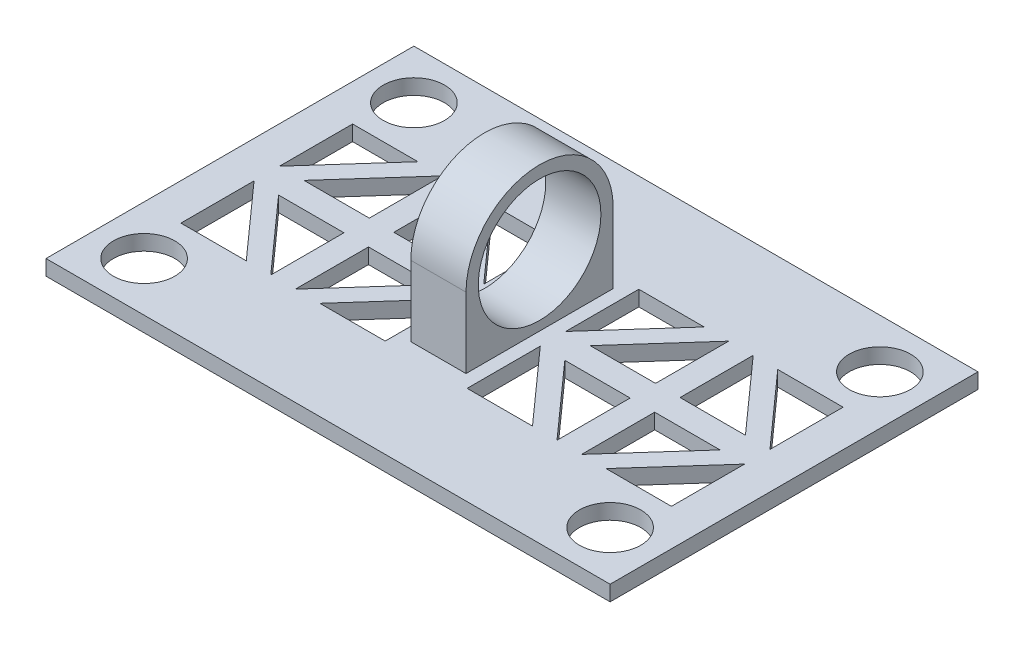
SolidWorks part; units mm, degrees
note: '?' marks a value the reader was unsure of.
ref_plane "Front Plane" through (0, 0, 0) normal (0, 0, 1) x (1, 0, 0)
ref_plane "Top Plane" through (0, 0, 0) normal (0, 1, 0) x (1, 0, 0)
ref_plane "Right Plane" through (0, 0, 0) normal (1, 0, 0) x (0, 0, -1)
sketch "Sketch1" plane through (0, 0, 0) normal (0, 1, 0) x (1, 0, 0)
  line L1 (0, 0) -> (-58.42, 0)
  line L2 (0, 0) -> (0, 38.1)
  line L3 (0, 38.1) -> (-58.42, 38.1)
  line L4 (-58.42, 0) -> (-58.42, 38.1)
  dimension "D1" = 58.42
  dimension "D2" = 38.1
extrude "Boss-Extrude1" add sketch "Sketch1" along normal blind 1.5875 contours L3 L4 L1 L2
ref_plane "Plane1" through (-29.21, 0, 0) normal (1, 0, 0) x (0, 0, -1)
sketch "Sketch2" plane through (-29.21, 0, 0) normal (1, 0, 0) x (0, 0, -1)
  line L0 (0, 0) -> (38.1, 0) construction
  line L1 (11.43, 8.89) -> (11.43, 0)
  line L2 (26.67, 8.89) -> (26.67, 0)
  line L3 (0, 0) -> (38.1, 0) construction
  line L4 (11.43, 0) -> (26.67, 0) construction
  line L5 (11.43, 0) -> (26.67, 0)
  circle A0 centre (19.05, 8.89) radius 7.62 construction
  arc A1 (11.43, 8.89) -> (26.67, 8.89) centre (19.05, 8.89) cw
  circle A2 centre (19.05, 8.89) radius 6.35
  point P13 (19.05, 0)
  point P15 (19.05, 0)
  dimension "D2" = 15.24
  dimension "D3" = 8.89
  dimension "D4" = 12.7
  dimension "D1" = 38.1
extrude "Boss-Extrude2" add sketch "Sketch2" along normal mid plane 5.715 contours A1 L2 L5 L1
sketch "Sketch4" plane through (-26.3525, 0, 0) normal (1, 0, 0) x (0, 0, -1)
  line L0 (19.05, 16.51) -> (19.05, 1.5875) construction
  line L1 (26.67, 1.5875) -> (11.43, 1.5875) construction
  line L2 (11.43, 8.89) -> (26.67, 8.89) construction
  arc A0 (26.67, 8.89) -> (11.43, 8.89) centre (19.05, 8.89) ccw construction
  circle A1 centre (19.05, 8.89) radius 6.35
  point P11 (19.05, 8.89)
  point P14 (0, 0)
  point P15 (0, 0)
  point P16 (19.05, 8.89)
  point P17 (19.05, 8.89)
  dimension "D1" = 12.7
extrude "Cut-Extrude1" cut sketch "Sketch4" against normal through all
sketch "Sketch5" plane through (0, 1.5875, 0) normal (0, 1, 0) x (1, 0, 0)
  line L0 (-54.61, 27.94) -> (-54.61, 20.3635)
  line L1 (-54.61, 20.3635) -> (-47.8408, 27.94)
  line L2 (-47.8408, 27.94) -> (-54.61, 27.94)
  line L3 (-45.3008, 27.94) -> (-52.07, 20.3635)
  line L4 (-52.07, 20.3635) -> (-45.3008, 20.3635)
  line L5 (-45.3008, 20.3635) -> (-45.3008, 27.94)
  line L6 (-42.7608, 20.3635) -> (-42.7608, 27.94)
  line L7 (-42.7608, 27.94) -> (-35.9916, 20.3635)
  line L8 (-35.9916, 20.3635) -> (-42.7608, 20.3635)
  line L9 (-40.2208, 27.94) -> (-33.4516, 20.3635)
  line L10 (-33.4516, 20.3635) -> (-33.4516, 27.94)
  line L11 (-33.4516, 27.94) -> (-40.2208, 27.94)
  line L12 (-58.42, 0) -> (-58.42, 38.1) construction
  line L13 (0, 38.1) -> (-58.42, 38.1) construction
  point P14 (0, 0)
  point P15 (0, 0)
  point P16 (-40.8475, 36.6275)
  point P17 (0, 0)
  point P20 (-55.88, 27.9835)
  dimension "D1" = 3.81
  dimension "D2" = 2.54
  dimension "D3" = 2.54
  dimension "D4" = 2.54
  dimension "D5" = 7.5765
  dimension "D6" = 10.16
  dimension "D7" = 10.16
extrude "Cut-Extrude2" cut sketch "Sketch5" against normal through all
ref_axis "Axis1" through (-32.0675, 1.5875, -19.05) along (-1, 0, 0)?
ref_plane "Plane2" through (0, 0, -19.05) normal (0, 0, -1) x (-1, 0, 0)
mirror "Mirror2" about plane through (0, 0, -19.05) normal (0, 0, -1) of "Cut-Extrude2"
mirror "Mirror3" about plane through (-29.21, 0, 0) normal (1, 0, 0) of "Cut-Extrude2"
mirror "Mirror4" about plane through (0, 0, -19.05) normal (0, 0, -1) of "Mirror3"
sketch "Sketch6" plane through (0, 1.5875, 0) normal (0, 1, 0) x (1, 0, 0)
  line L0 (-58.42, 0) -> (-58.42, 38.1) construction
  line L1 (0, 38.1) -> (-58.42, 38.1) construction
  line L2 (0, 0) -> (0, 38.1) construction
  line L5 (0, 0) -> (-58.42, 0) construction
  circle A0 centre (-53.34, 33.02) radius 3.175
  circle A1 centre (-5.08, 33.02) radius 3.175
  circle A2 centre (-5.08, 5.08) radius 3.175
  circle A3 centre (-53.34, 5.08) radius 3.175
  point P17 (-5.2187, 1.1098)
  point P18 (0, 0)
  dimension "D1" = 6.35
  dimension "D2" = 5.08
  dimension "D3" = 5.08
  dimension "D4" = 5.08
  dimension "D5" = 5.08
  dimension "D6" = 5.08
  dimension "D7" = 5.08
  dimension "D8" = 5.08
  dimension "D9" = 5.08
extrude "Cut-Extrude3" cut sketch "Sketch6" against normal through all
